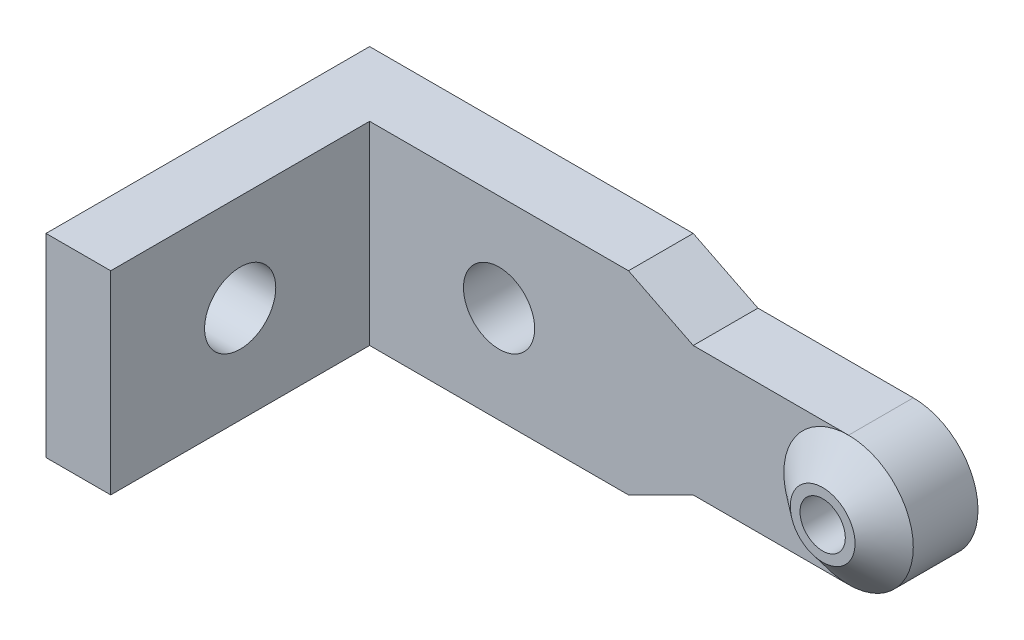
SolidWorks part; units mm, degrees
material "ABS"
ref_plane "Front Plane" through (0, 0, 0) normal (0, 0, 1) x (1, 0, 0)
ref_plane "Top Plane" through (0, 0, 0) normal (0, 1, 0) x (1, 0, 0)
ref_plane "Right Plane" through (0, 0, 0) normal (1, 0, 0) x (0, 0, -1)
sketch "Sketch1" plane through (0, 0, 0) normal (0, 1, 0) x (1, 0, 0)
  line L0 (0, 0) -> (0, -25)
  line L1 (0, -25) -> (5, -25)
  line L2 (5, -25) -> (5, -5)
  line L3 (5, -5) -> (47, -5)
  line L4 (47, -5) -> (47, 0)
  line L5 (47, 0) -> (0, 0)
  line L6 (25, 8.7838) -> (25, -25.5405) construction
  line L7 (42, 7.9279) -> (42, -15.6757) construction
  dimension "D1" = 20
  dimension "D2" = 20
  dimension "D3" = 5
  dimension "D4" = 17
  dimension "D5" = 5
extrude "Boss-Extrude1" add sketch "Sketch1" along normal blind 15
sketch "Sketch2" plane through (5, 0, 0) normal (1, 0, 0) x (0, 0, -1)
  line L1 (-25, 15) -> (-25, 0) construction
  circle A0 centre (-15, 7.5) radius 2.75
  point P2 (0, 0)
  point P3 (-25, 7.5)
  dimension "D2" = 10
  dimension "D3" = 5.5
extrude "Cut-Extrude1" cut sketch "Sketch2" against normal blind 10
sketch "Sketch3" plane through (0, 0, 5) normal (0, 0, 1) x (1, 0, 0)
  line L0 (5, 15) -> (5, 0) construction
  line L1 (5, 15) -> (5, 0) construction
  circle A0 centre (15, 7.5) radius 2.75
  point P6 (5, 7.5)
  dimension "D1" = 5.5
  dimension "D2" = 10
extrude "Cut-Extrude2" cut sketch "Sketch3" against normal blind 10
sketch "Sketch4" plane through (0, 0, 0) normal (1, 0, 0) x (0, 0, -1)
  circle A0 centre (-15, 7.5) radius 5.5
  dimension "D1" = 11
extrude "Cut-Extrude3" cut sketch "Sketch4" along normal blind 1
sketch "Sketch5" plane through (0, 0, 0) normal (0, 0, -1) x (-1, 0, 0)
  circle A0 centre (-15, 7.5) radius 5.5
  dimension "D1" = 11
extrude "Cut-Extrude4" cut sketch "Sketch5" against normal blind 1
sketch "Sketch6" plane through (0, 0, 0) normal (0, 0, -1) x (-1, 0, 0)
  line L0 (-47, 15) -> (-47, 0) construction
  circle A0 centre (-42, 7.5) radius 1.75
  circle A1 centre (-15, 7.5) radius 2.75 construction
  point P4 (0, 0)
  point P7 (-47, 7.5)
  dimension "D1" = 27
  dimension "D2" = 3.5
extrude "Cut-Extrude5" cut sketch "Sketch6" against normal blind 12
sketch "Sketch7" plane through (0, 0, 5) normal (0, 0, 1) x (1, 0, 0)
  circle A0 centre (42, 7.5) radius 1.75
  circle A1 centre (42, 7.5) radius 2.5
  dimension "D1" = 5
extrude "Boss-Extrude2" add sketch "Sketch7" along normal blind 2
sketch "Sketch8" plane through (0, 0, 0) normal (0, 0, -1) x (-1, 0, 0)
  line L0 (-47, 2.5) -> (-30, 2.5)
  line L1 (-47, 15) -> (-47, 0) construction
  line L2 (-30, 2.5) -> (-25, 0)
  line L3 (-47, 0) -> (0, 0) construction
  line L4 (-25, 0) -> (-47, 0)
  line L5 (-47, 0) -> (-47, 2.5)
  line L6 (-47, 12.5) -> (-47, 15)
  line L7 (-47, 15) -> (-25, 15)
  line L8 (-47, 15) -> (0, 15) construction
  line L9 (-25, 15) -> (-30, 12.5)
  line L10 (-47, 12.5) -> (-30, 12.5)
  circle A0 centre (-15, 7.5) radius 2.75 construction
  point P16 (-28.9829, 12.5)
  dimension "D1" = 10
  dimension "D2" = 10
  dimension "D3" = 17
extrude "Cut-Extrude6" cut sketch "Sketch8" against normal blind 12
fillet "Fillet1" 2 edges at (47, 12.5, 2.5) (47, 2.5, 2.5) type full round first side face at (38.5, 12.5, 2.5) second side face at (38.5, 2.5, 2.5) middle face at (47, 7.5, 2.5)
chamfer "Chamfer2" distance 2.5 distance2 2 1 edges at (39.5, 7.5, 5) first distance on face at (26.125, 7.5, 5)
